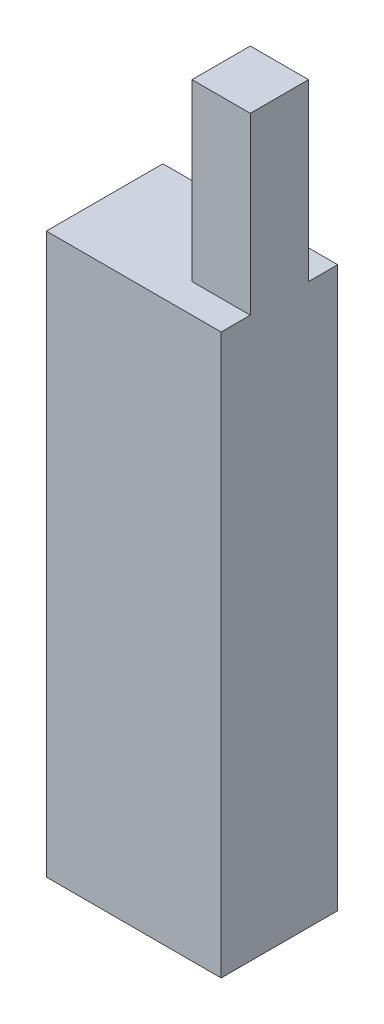
SolidWorks part; units mm, degrees
ref_plane "Front Plane" through (0, 0, 0) normal (0, 0, 1) x (1, 0, 0)
ref_plane "Top Plane" through (0, 0, 0) normal (0, 1, 0) x (1, 0, 0)
ref_plane "Right Plane" through (0, 0, 0) normal (1, 0, 0) x (0, 0, -1)
sketch "Sketch3" plane through (0, 0, 0) normal (0, 0, 1) x (1, 0, 0)
  line L0 (0, 0) -> (0, -5)
  line L1 (0, -5) -> (20, -5)
  line L2 (20, -5) -> (20, -25)
  line L3 (0, 0) -> (20, 0)
  line L4 (20, 0) -> (20, 30)
  line L5 (20, 30) -> (30, 30)
  line L6 (30, 30) -> (30, -25)
  line L7 (30, -25) -> (20, -25)
  dimension "D1" = 20
  dimension "D2" = 20
  dimension "D3" = 20
  dimension "D4" = 5
  dimension "D5" = 10
  dimension "D6" = 55
extrude "Boss-Extrude3" add sketch "Sketch3" along normal blind 10
sketch "Sketch5" plane through (0, 0, 10) normal (0, 0, 1) x (1, 0, 0)
  line L5 (0, 0) -> (30, 0)
  line L6 (0, 0) -> (0, -25)
  line L7 (0, -25) -> (30, -25)
  line L8 (30, 0) -> (30, -25)
extrude "Boss-Extrude5" add sketch "Sketch5" along normal blind 5
sketch "Sketch7" plane through (0, 0, 0) normal (0, 0, -1) x (-1, 0, 0)
  line L0 (-20, 0) -> (-30, 0)
  line L1 (-30, 0) -> (-30, -25)
  line L2 (-30, -25) -> (-20, -25)
  line L3 (-20, -25) -> (-20, -5)
  line L4 (-20, -5) -> (0, -5)
  line L5 (0, -5) -> (0, 0)
  line L6 (0, 0) -> (-20.7589, 0)
  line M8 (0, 0) -> (-20, 0)
  line M11 (-30, 30) -> (-30, -25)
  line M12 (-30, -25) -> (-20, -25)
  line M13 (-20, -25) -> (-20, -5)
  line M14 (-20, -5) -> (0, -5)
  line M15 (0, -5) -> (0, 0)
extrude "Boss-Extrude7" add sketch "Sketch7" along normal blind 5 contours L0 M8 M11 M12 M13 M14 M15 region at (20.7143, -9.6429, 0)
sketch "Sketch10" plane through (0, -25, 0) normal (0, -1, 0) x (1, 0, 0)
  line L0 (0, 10) -> (20, 10)
  line L1 (20, 10) -> (20, -5)
  line L2 (30, -5) -> (20, -5) construction
  line L3 (20, -5) -> (30, -5)
  line L4 (30, -5) -> (30, 15)
  line L5 (30, 15) -> (0, 15)
  line L6 (0, 15) -> (0, 10)
extrude "Boss-Extrude8" add sketch "Sketch10" along normal up to surface (71 mm away)
